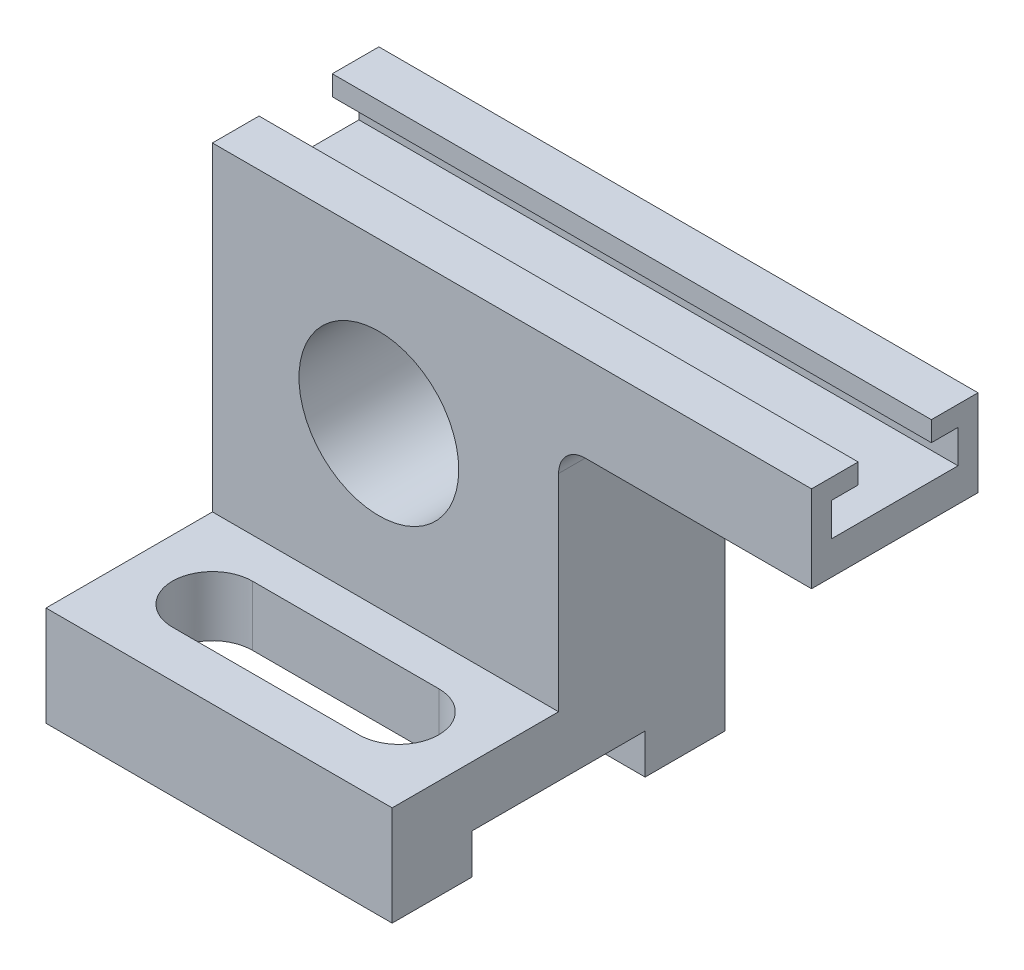
SolidWorks part; units mm, degrees
ref_plane "Front Plane" through (0, 0, 0) normal (0, 0, 1) x (1, 0, 0)
ref_plane "Top Plane" through (0, 0, 0) normal (0, 1, 0) x (1, 0, 0)
ref_plane "Right Plane" through (0, 0, 0) normal (1, 0, 0) x (0, 0, -1)
sketch "Sketch1" plane through (0, 0, 0) normal (0, 0, 1) x (1, 0, 0)
  line L0 (0, 0) -> (104, 0)
  line L1 (104, 0) -> (104, 100)
  line L2 (104, 100) -> (180, 100)
  line L3 (180, 100) -> (180, 126)
  line L4 (180, 126) -> (0, 126)
  line L5 (0, 126) -> (0, 0)
  line L6 (0, 30) -> (104, 30)
  dimension "D1" = 180
  dimension "D2" = 126
  dimension "D3" = 26
  dimension "D4" = 104
  dimension "D5" = 30
extrude "Boss-Extrude3" add sketch "Sketch1" along normal blind 50 contours L5 L6 L1 L2 L3 L4 region at (66.8696, 83.7826, 0)
extrude "Boss-Extrude4" add sketch "Sketch1<5>" along normal blind 100 contours L6 L5 L0 L1 region at (52, 15, 0)
sketch "Sketch1<5>" plane through (0, 0, 0) normal (0, 0, 1) x (1, 0, 0) same geometry as "Sketch1"
sketch "Sketch4" plane through (180, 0, 0) normal (1, 0, 0) x (0, 0, -1)
  line L0 (-36, 126) -> (-36, 120)
  line L1 (-50, 126) -> (0, 126) construction
  line L2 (-36, 120) -> (-44, 120)
  line L3 (-44, 120) -> (-44, 110)
  line L4 (-44, 110) -> (-6, 110)
  line L5 (-6, 110) -> (-6, 120)
  line L6 (-6, 120) -> (-14, 120)
  line L7 (-14, 120) -> (-14, 126)
  line L8 (-76, 0) -> (-76, 12)
  line L9 (-100, 0) -> (0, 0) construction
  line L10 (-76, 12) -> (-24, 12)
  line L11 (-24, 12) -> (-24, 0)
  line L12 (-76, 0) -> (-24, 0)
  line L13 (-36, 126) -> (-14, 126)
  line L14 (-100, 0) -> (-100, 30) construction
  line L15 (-50, 100) -> (-50, 126) construction
  line L16 (-50, 100) -> (0, 100) construction
  dimension "D1" = 52
  dimension "D2" = 24
  dimension "D3" = 12
  dimension "D4" = 6
  dimension "D5" = 38
  dimension "D6" = 14
  dimension "D7" = 22
  dimension "D8" = 10
  dimension "D9" = 10
extrude "Cut-Extrude1" cut sketch "Sketch4" against normal through all contours L12 L11 L10 L8
extrude "Cut-Extrude2" cut sketch "Sketch4<5>" against normal through all contours L4 L5 L6 L7 L13 L0 L2 L3
sketch "Sketch4<5>" plane through (180, 0, 0) normal (1, 0, 0) x (0, 0, -1) same geometry as "Sketch4"
sketch "Sketch5" plane through (0, 30, 0) normal (0, 1, 0) x (1, 0, 0)
  line L0 (24, -74) -> (80, -74) construction
  line L1 (24, -62) -> (80, -62)
  line L2 (24, -86) -> (80, -86)
  arc A0 (24, -62) -> (24, -86) centre (24, -74) ccw
  arc A1 (80, -86) -> (80, -62) centre (80, -74) ccw
  point P2 (52, -74)
  dimension "D1" = 24
  dimension "D2" = 56
  dimension "D3" = 24
  dimension "D4" = 24
extrude "Cut-Extrude3" cut sketch "Sketch5" against normal through all contours A0 L2 A1 L1
sketch "Sketch7" plane through (0, 0, 50) normal (0, 0, 1) x (1, 0, 0)
  line L0 (0, 126) -> (0, 0) construction
  line L1 (0, 30) -> (104, 30) construction
  circle A0 centre (50, 78) radius 24
  dimension "D1" = 48
  dimension "D2" = 50
  dimension "D3" = 48
extrude "Cut-Extrude4" cut sketch "Sketch7" against normal through all
fillet "Fillet3" radius 8 1 edges at (104, 100, 25)
